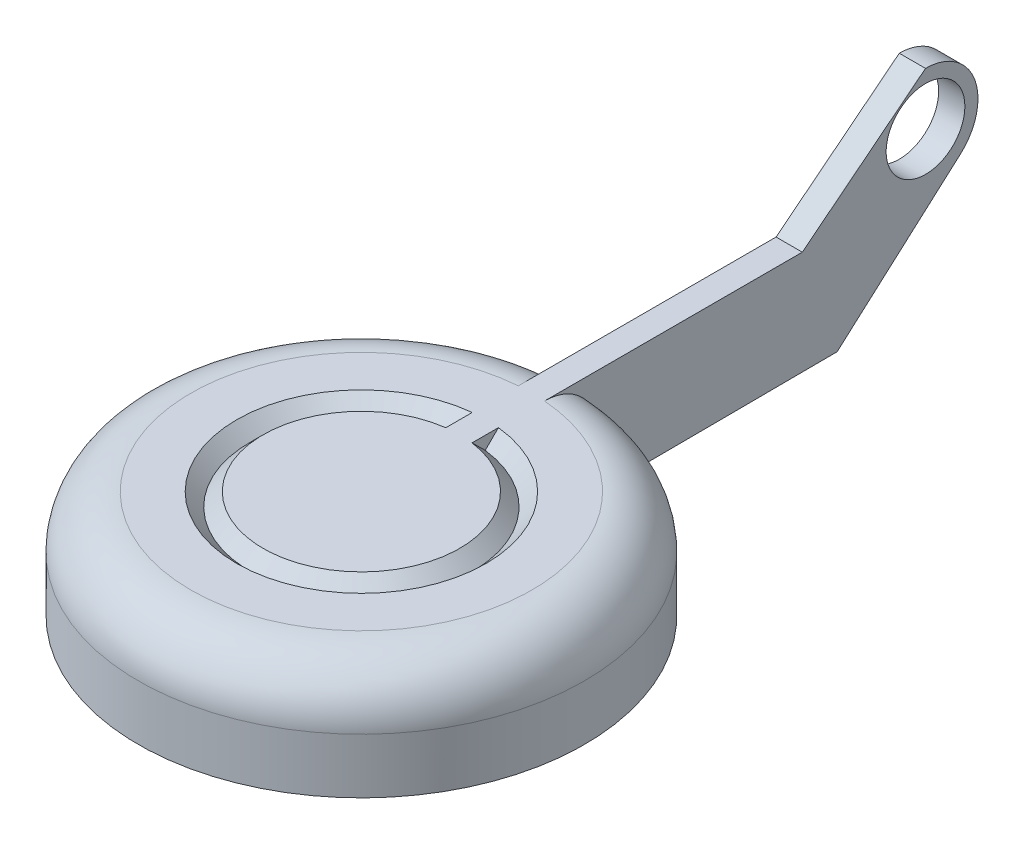
SolidWorks part; units mm, degrees
ref_plane "Front Plane" through (0, 0, 0) normal (0, 0, 1) x (1, 0, 0)
ref_plane "Top Plane" through (0, 0, 0) normal (0, 1, 0) x (1, 0, 0)
ref_plane "Right Plane" through (0, 0, 0) normal (1, 0, 0) x (0, 0, -1)
sketch "Sketch4" plane through (0, 0, 0) normal (1, 0, 0) x (0, 0, -1)
  line L0 (0, 0) -> (-3.75, 0)
  line L1 (-3.75, 0) -> (-4.25, -0.5)
  line L2 (-4.25, -0.5) -> (-4.75, 0)
  line L3 (-4.75, 0) -> (-8.5, 0)
  line L4 (-8.5, 0) -> (-8.5, -4)
  line L5 (-8.5, -4) -> (0, -4)
  line L6 (0, 0) -> (0, -4)
  line L7 (-8.5, -0.5) -> (0, -0.5) construction
  line L8 (0, 1.8905) -> (0, -6.6755) construction
  point P3 (-4.25, -0.5)
  dimension "D1" = 8.5
  dimension "D2" = 0.5
  dimension "D3" = 4
revolve "Revolve1" add sketch "Sketch4" angle 360 about L8
fillet "Fillet1" radius 2 1 edges at (0, 0, 8.5)
sketch "Sketch5" plane through (0, -4, 0) normal (0, -1, 0) x (1, 0, 0)
  circle A0 centre (0, 0) radius 8.5
  circle A1 centre (0, 0) radius 7
  dimension "D1" = 14
extrude "Boss-Extrude1" add sketch "Sketch5" along normal blind 0.1 separate body
sketch "Sketch6" plane through (0, 0, 0) normal (1, 0, 0) x (0, 0, -1)
  line L0 (0, 0) -> (16.304, 0)
  line L1 (8.5, -4) -> (17.6329, -3.95)
  line L2 (8.5, -4) -> (8.5, -2) construction
  line L3 (8.5, -4) -> (-8.5, -4) construction
  line L4 (17.6329, -3.95) -> (22.3287, 0.2237)
  line L5 (0, 0) -> (0, -0.9077)
  line L6 (0, -0.9077) -> (7.1744, -0.9077)
  line L7 (7.1744, -0.9077) -> (8.5, -4)
  line L8 (3.75, 0) -> (-3.75, 0) construction
  line L9 (16.304, 0) -> (21, 3.7186)
  circle A0 centre (21, 1.7186) radius 1.5
  circle A1 centre (21, 1.7186) radius 2
  point P4 (20.9702, -2)
  point P5 (20.9702, -2)
  point P6 (21, -3.95)
  point P7 (21, -1.95)
  point P17 (21, 1.7186)
  dimension "D1" = 3
  dimension "D2" = 4
  dimension "D3" = 21
extrude "Boss-Extrude2" add sketch "Sketch6" along normal blind 0.5 and the other way blind 0.5 contours L0 L5 L6 L7 L1 L4 A1 | A1 A0 region at (0, -1.5368, -12.8757) region at (0, 2.9035, -20.0617)
